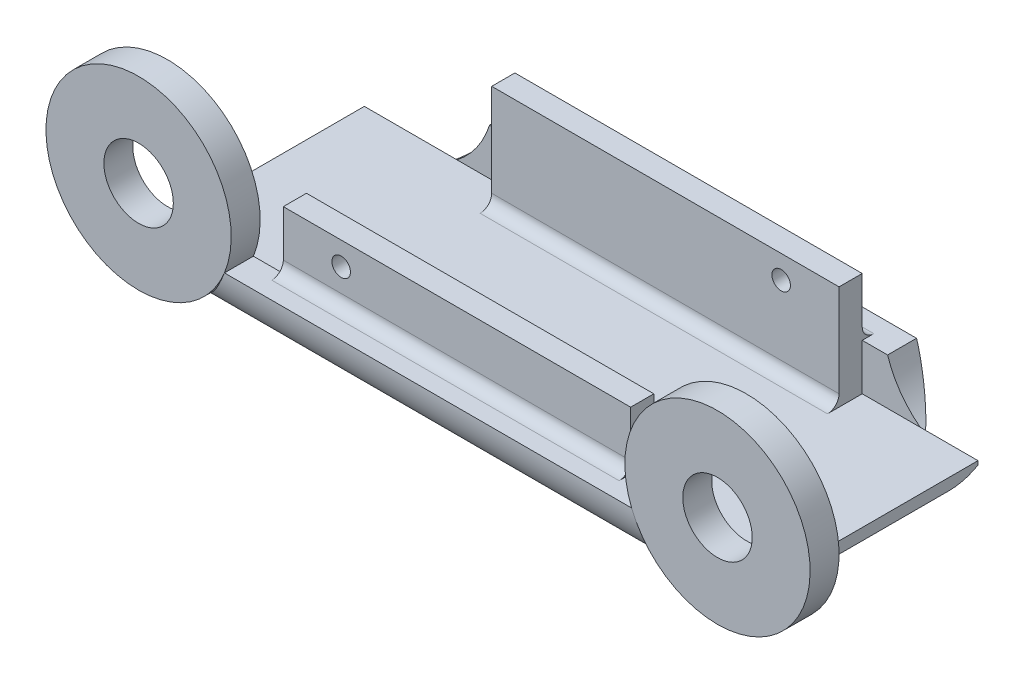
SolidWorks part; units mm, degrees
ref_plane "前视基准面" through (0, 0, 0) normal (0, 0, 1) x (1, 0, 0)
ref_plane "上视基准面" through (0, 0, 0) normal (0, 1, 0) x (1, 0, 0)
ref_plane "右视基准面" through (0, 0, 0) normal (1, 0, 0) x (0, 0, -1)
sketch "草图1" plane through (0, 0, 0) normal (0, 1, 0) x (1, 0, 0)
  line L1 (25, -12.5) -> (-25, -12.5)
  line L2 (25, -12.5) -> (25, 12.5)
  line L3 (25, 12.5) -> (-25, 12.5)
  line L4 (-25, -12.5) -> (-25, 12.5)
  line L5 (25, -12.5) -> (-25, 12.5) construction
  line L6 (25, 12.5) -> (-25, -12.5) construction
  point P0 (0, 0)
extrude "凸台-拉伸1" add sketch "草图1" along normal blind 10
sketch "草图2" plane through (25, 0, 0) normal (1, 0, 0) x (0, 0, -1)
  line L0 (-12.5, 0) -> (12.5, 0) construction
  line L1 (0, 0) -> (0, 6.1663) construction
  line L2 (-12.5, 0) -> (-7.5, 0)
  line L3 (-12.5, 5) -> (-12.5, 0)
  line L5 (12.5, 5) -> (12.5, 0)
  line L6 (12.5, 0) -> (7.5, 0)
  arc A0 (7.5, 0) -> (12.5, 5) centre (7.5, 5) ccw
  arc A1 (-7.5, 0) -> (-12.5, 5) centre (-7.5, 5) cw
  point P9 (12.5, 0)
  point P11 (0, 0)
  dimension "D1" = 5
extrude "切除-拉伸1" cut sketch "草图2" against normal up to next
sketch "草图3" plane through (25, 0, 0) normal (1, 0, 0) x (0, 0, -1)
  line L0 (-8, 10) -> (8, 10)
  line L1 (-12.5, 10) -> (12.5, 10) construction
  line L2 (8, 10) -> (8, 1)
  line L3 (0, 10) -> (0, 4.0635) construction
  line L4 (8, 1) -> (-8, 1)
  line L5 (-8, 1) -> (-8, 10)
  point P15 (0, 1)
extrude "切除-拉伸2" cut sketch "草图3" against normal through all
sketch "草图14" plane through (0, 0, -12.5) normal (0, 0, -1) x (-1, 0, 0)
  line L1 (-25, 10) -> (25, 10)
  line L2 (-25, 10) -> (-25, 5)
  line L3 (-25, 5) -> (25, 5)
  line L4 (25, 10) -> (25, 5)
extrude "切除-拉伸5" cut sketch "草图14" against normal blind 2.5
sketch "草图15" plane through (0, 0, 12.5) normal (0, 0, 1) x (1, 0, 0)
  line L1 (25, 5) -> (-25, 5)
  line L2 (25, 5) -> (25, 10)
  line L3 (25, 10) -> (-25, 10)
  line L4 (-25, 5) -> (-25, 10)
extrude "切除-拉伸6" cut sketch "草图15" against normal blind 2.5
hole_wizard "M2 螺纹孔1" positions "草图10" profile "草图11" tap size "M2" standard "ISO" end condition up to next
sketch "草图10" plane through (0, 0, -10) normal (0, 0, -1) x (-1, 0, 0)
  point P0 (-10, 8)
sketch "草图11" plane through (10, 8, -10) normal (1, 0, 0) x (0, 1, 0)
  line L0 (0, 0) -> (0, 2)
  line L1 (0, 2) -> (0.8, 2)
  line L2 (0.8, 2) -> (0.8, 0)
  line L5 (0.8, 0) -> (0, 0)
  line L11 (0, -6.35) -> (0, 107.95) construction
  dimension "通孔螺纹孔钻头直径" = 1.6
  dimension "通孔螺纹孔钻头深度" = 2
cosmetic thread "孔螺蚊线1" parameters "D1"=2, "D2"=2
hole_wizard "M2 螺纹孔2" positions "草图12" profile "草图13" tap size "M2" standard "ISO" end condition up to next
sketch "草图12" plane through (0, 0, 10) normal (0, 0, 1) x (1, 0, 0)
  point P0 (-10, 8)
sketch "草图13" plane through (-10, 8, 10) normal (1, 0, 0) x (0, -1, 0)
  line L0 (0, 0) -> (0, 2)
  line L1 (0, 2) -> (0.8, 2)
  line L2 (0.8, 2) -> (0.8, 0)
  line L5 (0.8, 0) -> (0, 0)
  line L11 (0, -6.35) -> (0, 107.95) construction
  dimension "通孔螺纹孔钻头直径" = 1.6
  dimension "通孔螺纹孔钻头深度" = 2
cosmetic thread "孔螺蚊线2" parameters "D1"=2, "D2"=2
sketch "草图17" plane through (0, 0, -10) normal (0, 0, -1) x (-1, 0, 0)
  line L1 (-25, 10) -> (-25, 5) construction
  circle A0 centre (-25, 7.5) radius 8.2
  circle A1 centre (25, 7.5) radius 8.2
sketch "草图19" plane through (0, 0, -8) normal (0, 0, 1) x (1, 0, 0)
  line L1 (-25, 10) -> (-15, 10)
  line L2 (-25, 10) -> (-25, 1)
  line L3 (-25, 1) -> (-15, 1)
  line L4 (-15, 10) -> (-15, 1)
  line L6 (25, 10) -> (15, 10)
  line L7 (25, 10) -> (25, 1)
  line L8 (25, 1) -> (15, 1)
  line L9 (15, 10) -> (15, 1)
extrude "切除-拉伸10" cut sketch "草图19" against normal blind 2
sketch "草图21" plane through (0, 0, 10) normal (0, 0, 1) x (1, 0, 0)
  line L0 (25, 5) -> (25, 10) construction
  circle A0 centre (25, 8) radius 8
  circle A1 centre (-25, 8) radius 8
extrude "凸台-拉伸5" add sketch "草图21" along normal blind 2.5
sketch "草图22" plane through (0, 0, 10) normal (0, 0, 1) x (1, 0, 0)
  line L1 (-25, 10) -> (-15, 10)
  line L2 (-25, 10) -> (-25, 1)
  line L3 (-25, 1) -> (-15, 1)
  line L4 (-15, 10) -> (-15, 1)
  line L6 (25, 10) -> (15, 10)
  line L7 (25, 10) -> (25, 1)
  line L8 (25, 1) -> (15, 1)
  line L9 (15, 10) -> (15, 1)
extrude "切除-拉伸12" cut sketch "草图22" against normal blind 2
sketch "草图23" plane through (0, 0, 12.5) normal (0, 0, 1) x (1, 0, 0)
  circle A0 centre (25, 8) radius 3
  circle A1 centre (-25, 8) radius 3
extrude "切除-拉伸13" cut sketch "草图23" against normal up to next
extrude "切除-拉伸15" cut sketch "草图17" along normal blind 10
sketch "草图24" plane through (-25, 0, 0) normal (-1, 0, 0) x (0, 0, 1)
  line L0 (0, 0) -> (0, 6.3427) construction
  line L1 (10, 1) -> (-10, 1)
  line L2 (10, 1) -> (10, 0.6699)
  line L3 (7.5, 0) -> (-7.5, 0)
  line L4 (-10, 1) -> (-10, 0.6699)
  arc A0 (7.5, 0) -> (10, 0.6699) centre (7.5, 5) ccw construction
  arc A1 (7.5, 0) -> (10, 0.6699) centre (7.5, 5) ccw
  arc A2 (-7.5, 0) -> (-10, 0.6699) centre (-7.5, 5) cw
extrude "凸台-拉伸6" add sketch "草图24" along normal blind 3
fillet "圆角1" radius 1 2 edges at (0, 1, 8) (0, 1, -8)
fillet "圆角2" radius 1 2 edges at (0, 5, 10) (0, 5, -10)
